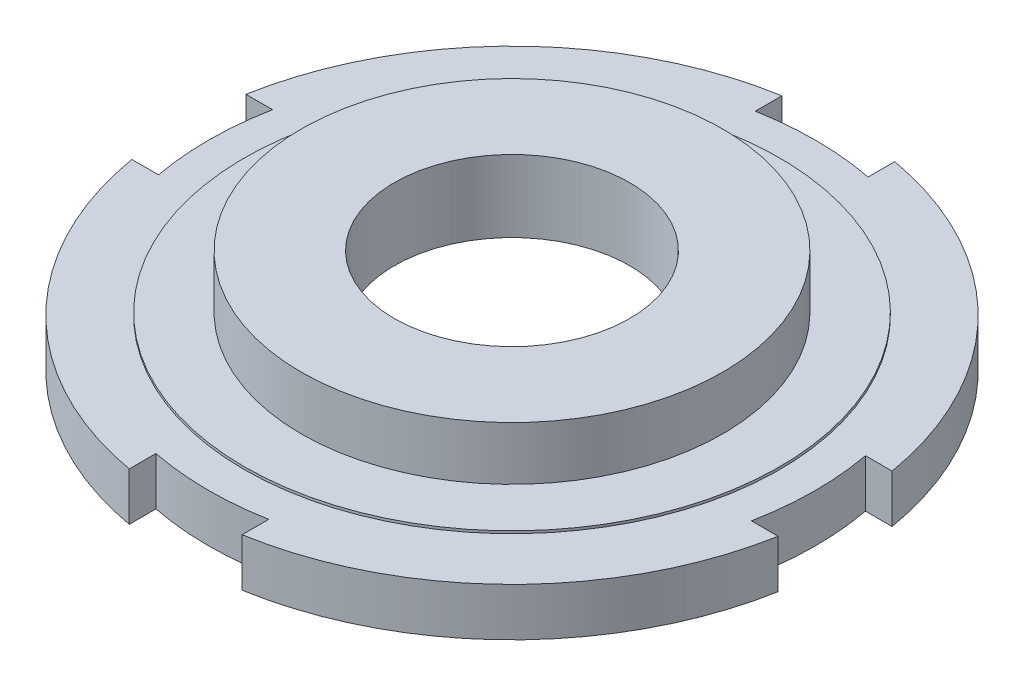
SolidWorks part; units mm, degrees
ref_plane "Front Plane" through (0, 0, 0) normal (0, 0, 1) x (1, 0, 0)
ref_plane "Top Plane" through (0, 0, 0) normal (0, 1, 0) x (1, 0, 0)
ref_plane "Right Plane" through (0, 0, 0) normal (1, 0, 0) x (0, 0, -1)
sketch "Sketch1" plane through (0, 0, 0) normal (0, 1, 0) x (1, 0, 0)
  line L0 (35.4054, 6.5405) -> (38.5653, 6.5405)
  line L1 (35.3329, -6.9215) -> (38.4988, -6.9215)
  line L2 (-55, 0) -> (55, 0) construction
  line L3 (6.5405, -35.4054) -> (6.5405, -38.5653)
  line L4 (-6.9215, -35.3329) -> (-6.9215, -38.4988)
  line L5 (-35.4054, -6.5405) -> (-38.5653, -6.5405)
  line L6 (-35.3329, 6.9215) -> (-38.4988, 6.9215)
  line L7 (-6.5405, 35.4054) -> (-6.5405, 38.5653)
  line L8 (6.9215, 35.3329) -> (6.9215, 38.4988)
  arc A1 (-38.5653, -6.5405) -> (-6.9215, -38.4988) centre (0, 0) ccw
  circle A2 centre (0, 0) radius 13.97
  arc A3 (-35.3329, 6.9215) -> (-35.4054, -6.5405) centre (0, 0) ccw
  arc A4 (6.9215, 35.3329) -> (-6.5405, 35.4054) centre (0, 0) ccw
  arc A5 (35.3329, -6.9215) -> (35.4054, 6.5405) centre (0, 0) ccw
  arc A6 (-6.9215, -35.3329) -> (6.5405, -35.4054) centre (0, 0) ccw
  arc A7 (6.5405, -38.5653) -> (38.4988, -6.9215) centre (0, 0) ccw
  arc A8 (38.5653, 6.5405) -> (6.9215, 38.4988) centre (0, 0) ccw
  arc A9 (-6.5405, 38.5653) -> (-38.4988, 6.9215) centre (0, 0) ccw
  point P26 (0, 0)
  dimension "D1" = 78.232
  dimension "D2" = 72.009
  dimension "D6" = 27.94
  dimension "D3" = 13.462
  dimension "D4" = 6.5405
  dimension "D5" = 4
ref_axis "Axis1" through (41.0751, 0, 0) along (-1, 0, 0)
ref_plane "Plane2" through (0, 0, 0) normal (0, -0.9903, 0.1392) x (-1, 0, 0)
ref_plane "Plane3" through (0, 6.2882, -0.8837) normal (0, -0.9903, 0.1392) x (-1, 0, 0)
extrude "Boss-Extrude2" add sketch "Sketch1" along normal blind 6
sketch "Sketch2" plane through (0, 0, 0) normal (0, -1, 0) x (1, 0, 0)
  line L3 (17.3777, -10.033) -> (-0.2866, -40.6283)
  line L4 (-4.5397, -40.3749) -> (8.1962, -18.3157)
  line L5 (3.2131, 0) -> (-3.2131, 0) construction
  arc A3 (8.1962, -18.3157) -> (17.3777, -10.033) centre (0, 0) cw
  arc A4 (-0.2866, -40.6283) -> (-4.5397, -40.3749) centre (0, 0) cw
  point P4 (8.5456, -25.3307)
  dimension "D1" = 20.066
  dimension "D2" = 3.81
  dimension "D3" = 60
extrude "Cut-Extrude1" cut sketch "Sketch2" against normal blind 3.81
sketch "Sketch3" plane through (0, 0, 0) normal (0, -1, 0) x (1, 0, 0)
  circle A0 centre (0, 0) radius 31.75
extrude "Cut-Extrude2" cut sketch "Sketch3" against normal blind 0.3
sketch "Sketch5" plane through (0, 6, 0) normal (0, 1, 0) x (1, 0, 0)
  circle A0 centre (0, 0) radius 25.001
  circle A1 centre (0, 0) radius 13.97 construction
  circle A2 centre (0, 0) radius 13.97
  dimension "D1" = 50.002
extrude "Boss-Extrude3" add sketch "Sketch5" along normal blind 6.35
sketch "Sketch6" plane through (0, 6, 0) normal (0, 1, 0) x (1, 0, 0)
  circle A0 centre (0, 0) radius 31.75
  circle A3 centre (0, 0) radius 50.8
  dimension "D1" = 63.5
  dimension "D2" = 101.6
extrude "Cut-Extrude3" cut sketch "Sketch6" against normal blind 0.3
